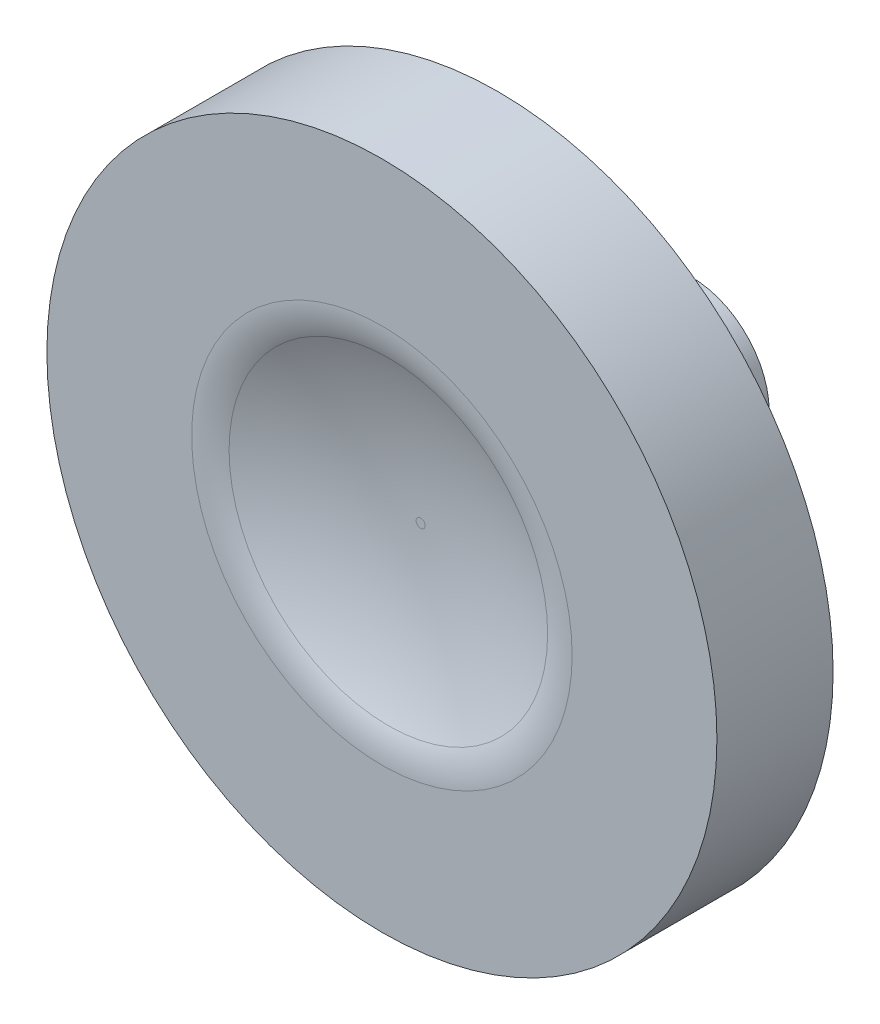
SolidWorks part; units mm, degrees
ref_plane "Front Plane" through (0, 0, 0) normal (0, 0, 1) x (1, 0, 0)
ref_plane "Top Plane" through (0, 0, 0) normal (0, 1, 0) x (1, 0, 0)
ref_plane "Right Plane" through (0, 0, 0) normal (1, 0, 0) x (0, 0, -1)
sketch "Sketch1" plane through (0, 0, 0) normal (0, 0, 1) x (1, 0, 0)
  circle A0 centre (0, 0) radius 10.9855
  circle A1 centre (0, 0) radius 4.0386
  dimension "D1" = 21.971
  dimension "D2" = 8.0772
extrude "Boss-Extrude1" add sketch "Sketch1" along normal blind 2.54 contours A1
extrude "Boss-Extrude2" add sketch "Sketch1<4>" along normal blind 3.81
sketch "Sketch1<4>" plane through (0, 0, 0) normal (0, 0, 1) x (1, 0, 0) same geometry as "Sketch1"
fillet "Fillet1" radius 2.54 1 edges at (4.0386, 0, 3.81)
fillet "Fillet2" radius 12.7 1 edges at (4.0386, 0, 2.54)
sketch "Sketch2" plane through (0, 0, 0) normal (0, 0, -1) x (-1, 0, 0)
extrude "Boss-Extrude3" add sketch "Sketch1<6>" against normal blind 2.54 contours A1
sketch "Sketch1<6>" plane through (0, 0, 0) normal (0, 0, 1) x (1, 0, 0) same geometry as "Sketch1"
sketch "Sketch3" plane through (0, 0, -2.54) normal (0, 0, -1) x (-1, 0, 0)
  circle A0 centre (0, 0) radius 2.54
  dimension "D1" = 5.08
sketch "Sketch7" plane through (0, 0, -2.54) normal (0, 0, -1) x (-1, 0, 0)
extrude "Boss-Extrude4" add sketch "Sketch3" along normal blind 3.81
